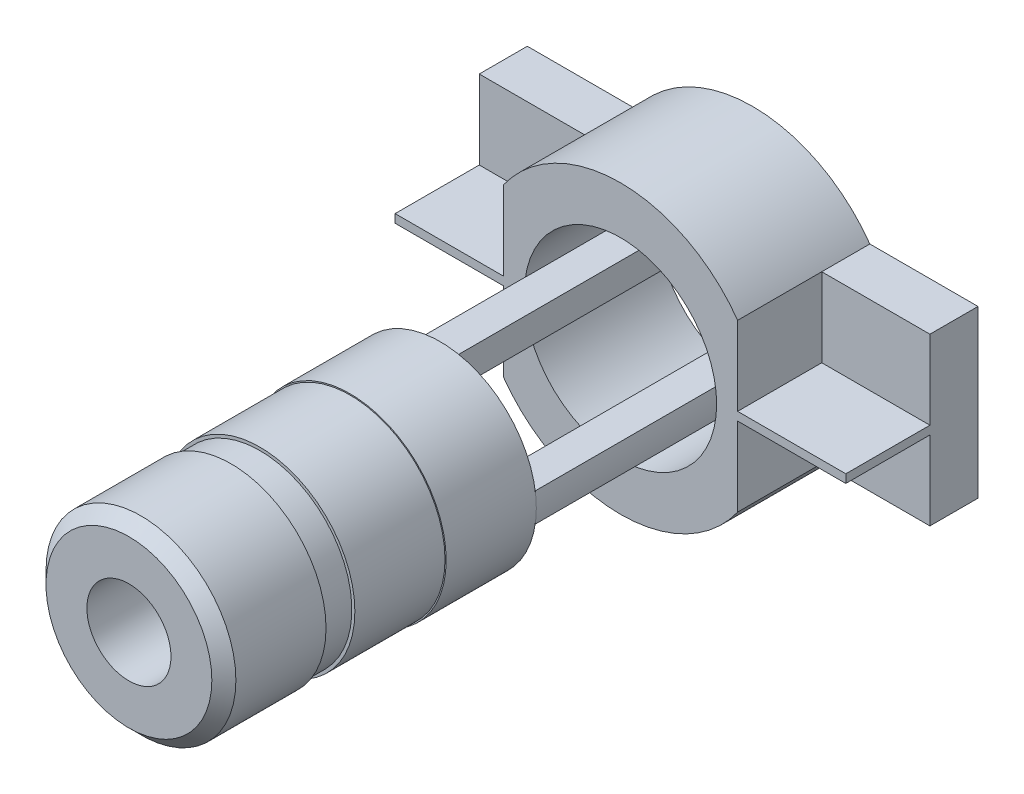
SolidWorks part; units mm, degrees
material "ASTM A36 Steel"
ref_plane "Front Plane" through (0, 0, 0) normal (0, 0, 1) x (1, 0, 0)
ref_plane "Top Plane" through (0, 0, 0) normal (0, 1, 0) x (1, 0, 0)
ref_plane "Right Plane" through (0, 0, 0) normal (1, 0, 0) x (0, 0, -1)
sketch "Sketch1" plane through (0, 0, 0) normal (0, 0, 1) x (1, 0, 0)
  circle A0 centre (0, 0) radius 7.9
  circle A1 centre (0, 0) radius 3.5
  dimension "D1" = 15.8
  dimension "D2" = 7
extrude "Boss-Extrude1" add sketch "Sketch1" along normal blind 18.4
chamfer "Chamfer1" distance 1 angle 45 1 edges at (7.9, 0, 18.4)
ref_plane "Plane7" [suppressed] through (0, 0, 7.5) normal (0, 0, -1) x (-1, 0, 0)
ref_plane "Plane8" through (0, 0, 9.9) normal (0, 0, -1) x (-1, 0, 0)
sketch "Sketch19" plane through (0, 0, 9.9) normal (0, 0, -1) x (-1, 0, 0)
  circle A0 centre (0, 0) radius 7.65
  circle A1 centre (0, 0) radius 7.9
  dimension "D1" = 15.3
extrude "Cut-Extrude6" cut sketch "Sketch19" along normal blind 2.4
sketch "Sketch20" plane through (0, 0, 0) normal (0, 0, -1) x (-1, 0, 0)
  circle A0 centre (0, 0) radius 7.9
  circle A1 centre (0, 0) radius 4.5
  dimension "D1" = 9
extrude "Boss-Extrude3" [suppressed] add sketch "Sketch20" along normal blind 28.6 separate body
sketch "Sketch21" [suppressed] plane through (0, 0, -28.6) normal (0, 0, -1) x (-1, 0, 0)
  line L1 (0, 3.0042) -> (-7.3065, 3.0042)
  line L9 (-7.3081, -3.0004) -> (0, -3.0004)
  line L12 (0, -3.0004) -> (7.3081, -3.0004)
  line L13 (0, 3.0042) -> (7.3065, 3.0042)
  circle A0 centre (0, 0) radius 7.9 construction
  arc A1 (-7.3065, 3.0042) -> (7.3065, 3.0042) centre (0, 0) cw
  arc A2 (-7.3081, -3.0004) -> (7.3081, -3.0004) centre (0, 0) ccw
extrude "Cut-Extrude7" [suppressed] cut sketch "Sketch21" against normal blind 28.6
ref_plane "Plane9" [suppressed] through (0, 0, -28.6) normal (0, 0, -1) x (-1, 0, 0)
sketch "Sketch22" [suppressed] plane through (0, 0, -28.6) normal (0, 0, -1) x (-1, 0, 0)
  circle A0 centre (0, 0) radius 12
  dimension "D1" = 24
extrude "Boss-Extrude4" [suppressed] add sketch "Sketch22" along normal blind 6
sketch "Sketch23" [suppressed] plane through (0, 0, -34.6) normal (0, 0, -1) x (-1, 0, 0)
  circle A0 centre (0, 0) radius 4.5
  dimension "D1" = 9
extrude "Cut-Extrude8" [suppressed] cut sketch "Sketch23" against normal up to next
sketch "Sketch24" plane through (0, 0, 0) normal (0, 0, -1) x (-1, 0, 0)
  circle A0 centre (0, 0) radius 8
  dimension "D1" = 16
extrude "Boss-Extrude5" add sketch "Sketch24" along normal blind 7.5 separate body
sketch "Sketch25" plane through (0, 0, -7.5) normal (0, 0, -1) x (-1, 0, 0)
  line L3 (-5.1095, 1.2) -> (-7.9095, 1.2)
  line L4 (-5.1095, -1.2) -> (-7.9095, -1.2)
  line L5 (0, 0) -> (-5.1095, 0) construction
  line L6 (-5.1095, 1.2) -> (-5.1095, 0)
  line L7 (-5.1095, 0) -> (-5.1095, -1.2)
  line L10 (5.1095, 1.2) -> (7.9095, 1.2)
  line L11 (5.1095, -1.2) -> (7.9095, -1.2)
  line L12 (0, 0) -> (5.1095, 0) construction
  line L13 (5.1095, 1.2) -> (5.1095, 0)
  line L14 (5.1095, -1.2) -> (5.1095, 0)
  circle A0 centre (0, 0) radius 8 construction
  arc A1 (-8, 0) -> (-7.9095, 1.2) centre (0, 0) cw
  arc A2 (-8, 0) -> (-7.9095, -1.2) centre (0, 0) ccw
  arc A3 (7.9095, 1.2) -> (7.9095, -1.2) centre (0, 0) cw
  dimension "D1" = 2.8
  dimension "D2" = 2.8
  dimension "D3" = 2.8
  dimension "D4" = 2.8
extrude "Boss-Extrude6" add sketch "Sketch25" along normal blind 26 separate body
ref_plane "Plane10" through (0, 0, -33.5) normal (0, 0, -1) x (-1, 0, 0)
sketch "Sketch26" plane through (0, 0, -33.5) normal (0, 0, -1) x (-1, 0, 0)
  circle A0 centre (0, 0) radius 11.95
  circle A1 centre (0, 0) radius 8
  dimension "D1" = 23.9
  dimension "D2" = 16
extrude "Boss-Extrude7" add sketch "Sketch26" against normal blind 11 separate body
sketch "Sketch27" plane through (0, 0, -22.5) normal (0, 0, 1) x (1, 0, 0)
  line L2 (-9.75, 0) -> (-9.75, 6.9094)
  line L3 (-9.75, 0) -> (-9.75, -6.9094)
  line L4 (9.75, 0) -> (9.75, 6.9094)
  line L5 (9.75, 0) -> (9.75, -6.9094)
  circle A0 centre (0, 0) radius 11.95 construction
  arc A1 (-9.75, 6.9094) -> (-9.75, -6.9094) centre (0, 0) ccw
  arc A2 (9.75, 6.9094) -> (9.75, -6.9094) centre (0, 0) cw
extrude "Cut-Extrude9" cut sketch "Sketch27" against normal through all
sketch "Sketch28" plane through (0, 0, -7.5) normal (0, 0, -1) x (-1, 0, 0)
  circle A0 centre (0, 0) radius 3.5
  dimension "D1" = 7
extrude "Cut-Extrude10" cut sketch "Sketch28" against normal through all
sketch "Sketch29" plane through (-9.75, 0, 0) normal (-1, 0, 0) x (0, 0, 1)
  line L0 (-33.5, 6.9094) -> (-29.5, 6.9094)
  line L1 (-33.5, 6.9094) -> (-22.5, 6.9094) construction
  line L2 (-29.5, 6.9094) -> (-29.5, -6.9094)
  line L3 (-33.5, -6.9094) -> (-22.5, -6.9094) construction
  line L4 (-29.5, -6.9094) -> (-33.5, -6.9094)
  line L5 (-33.5, -6.9094) -> (-33.5, 6.9094)
  dimension "D1" = 4
extrude "Boss-Extrude8" add sketch "Sketch29" along normal blind 9
sketch "Sketch30" plane through (9.75, 0, 0) normal (1, 0, 0) x (0, 0, -1)
  line L0 (33.5, 6.9094) -> (29.5, 6.9094)
  line L1 (33.5, 6.9094) -> (22.5, 6.9094) construction
  line L2 (29.5, 6.9094) -> (29.5, -6.9094)
  line L3 (33.5, -6.9094) -> (22.5, -6.9094) construction
  line L4 (29.5, -6.9094) -> (33.5, -6.9094)
  line L5 (33.5, -6.9094) -> (33.5, 6.9094)
  dimension "D1" = 4
extrude "Boss-Extrude9" add sketch "Sketch30" along normal blind 9
sketch "Sketch31" plane through (9.75, 0, 0) normal (1, 0, 0) x (0, 0, -1)
  line L0 (22.5, 0) -> (22.5, 0.35)
  line L1 (22.5, 6.9094) -> (22.5, -6.9094) construction
  line L2 (22.5, 0.35) -> (29.5, 0.35)
  line L3 (29.5, 6.9094) -> (29.5, -6.9094) construction
  line L4 (22.5, 0) -> (22.5, -0.35)
  line L5 (22.5, -0.35) -> (29.5, -0.35)
  line L6 (29.5, 6.9094) -> (29.5, -6.9094) construction
  line L7 (29.5, 0.35) -> (29.5, -0.35)
  dimension "D1" = 0.35
  dimension "D2" = 0.35
extrude "Boss-Extrude10" add sketch "Sketch31" along normal blind 9
sketch "Sketch32" plane through (-9.75, 0, 0) normal (-1, 0, 0) x (0, 0, 1)
  line L0 (-22.5, 0) -> (-22.5, 0.35)
  line L1 (-22.5, -6.9094) -> (-22.5, 6.9094) construction
  line L2 (-22.5, 0) -> (-22.5, -0.35)
  line L3 (-22.5, 0.35) -> (-29.5, 0.35)
  line L4 (-29.5, -6.9094) -> (-29.5, 6.9094) construction
  line L5 (-22.5, -0.35) -> (-29.5, -0.35)
  line L6 (-29.5, -6.9094) -> (-29.5, 6.9094) construction
  line L7 (-29.5, 0.35) -> (-29.5, -0.35)
  dimension "D1" = 0.35
  dimension "D2" = 0.35
extrude "Boss-Extrude11" add sketch "Sketch32" along normal blind 9
